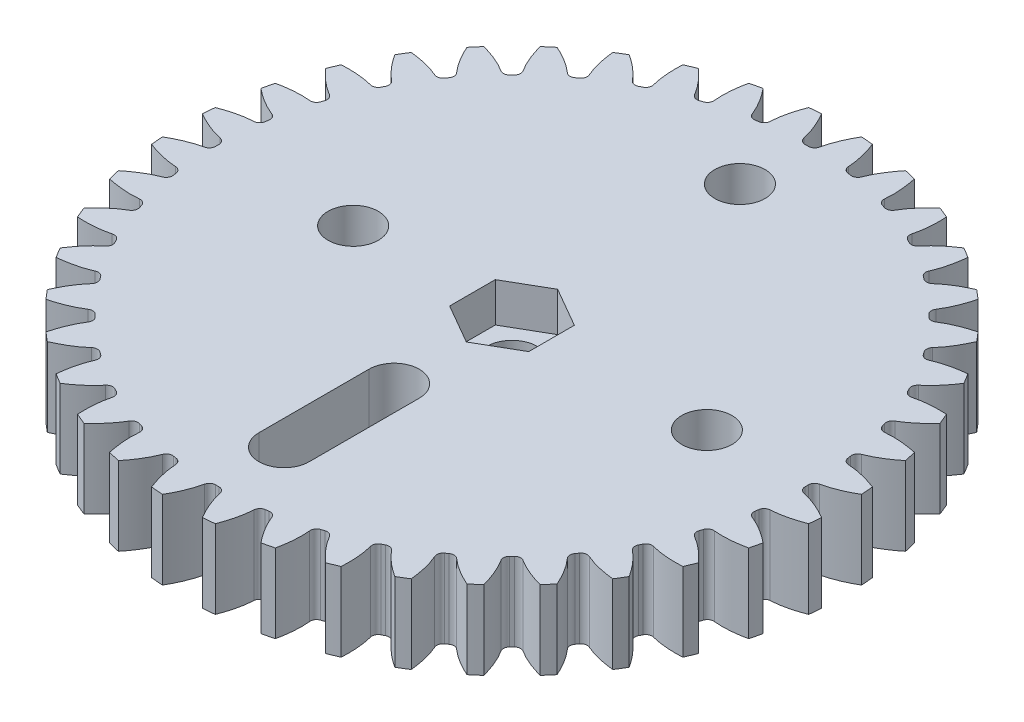
SolidWorks part; units mm, degrees
ref_plane "Front Plane" through (0, 0, 0) normal (0, 0, 1) x (1, 0, 0)
ref_plane "Top Plane" through (0, 0, 0) normal (0, 1, 0) x (1, 0, 0)
ref_plane "Right Plane" through (0, 0, 0) normal (1, 0, 0) x (0, 0, -1)
sketch "Sketch2" plane through (0, 0, 0) normal (0, 1, 0) x (1, 0, 0)
  circle A0 centre (0, 0) radius 53.34
  dimension "D1" = 106.68
extrude "Boss-Extrude1" add sketch "Sketch2" along normal blind 12.7
sketch "Sketch3" plane through (0, 0, 0) normal (0, -1, 0) x (-1, 0, 0)
  line L0 (0, 0) -> (47.7222, -1.163) construction
  line L1 (0, 0) -> (47.7222, 1.163) construction
  line L2 (47.7222, -1.163) -> (47.6109, -1.1603)
  line L3 (47.7222, 1.163) -> (47.6109, 1.1603)
  circle A0 centre (0, 0) radius 53.34
  circle A1 centre (0, 0) radius 50.8
  circle A2 centre (0, 0) radius 47.752
  circle A3 centre (0, 0) radius 47.625
  spline S0 degree 4 poles (47.7222, 1.163) (47.731, 1.1633) (47.7556, 1.1645) (47.802, 1.1678) (47.8777, 1.1747) (47.9741, 1.186) (48.0986, 1.2033) (48.2451, 1.2271) (48.4058, 1.257) (48.5805, 1.2934) (48.7546, 1.3332) (48.928, 1.3762) (49.1005, 1.4219) (49.3093, 1.4808) (49.5592, 1.5562) (49.8507, 1.6513) (50.1805, 1.7675) (50.5158, 1.8948) (50.845, 2.0273) (51.1768, 2.1695) (51.4972, 2.313) (51.8289, 2.4707) (52.1347, 2.6205) (52.4761, 2.7979) (52.7513, 2.9438) (53.113, 3.1463) (53.3263, 3.2689) (53.5754, 3.4159) (53.6857, 3.483) (53.7537, 3.5243) knots 0 0 0 0 0 0.005377 0.015084 0.028532 0.04661 0.064855 0.092111 0.119476 0.146842 0.174209 0.201575 0.228941 0.256307 0.307035 0.361767 0.4165 0.471232 0.525964 0.580697 0.635429 0.690161 0.744894 0.799626 0.854358 0.909091 0.954545 1 1 1 1 1 construction
  spline S1 degree 4 poles (47.7222, 1.163) (47.731, 1.1633) (47.7556, 1.1645) (47.802, 1.1678) (47.8777, 1.1747) (47.9741, 1.186) (48.0986, 1.2033) (48.2451, 1.2271) (48.4058, 1.257) (48.5805, 1.2934) (48.7546, 1.3332) (48.928, 1.3762) (49.1005, 1.4219) (49.3093, 1.4808) (49.5592, 1.5562) (49.8507, 1.6513) (50.1805, 1.7675) (50.5158, 1.8948) (50.845, 2.0273) (51.1768, 2.1695) (51.4972, 2.313) (51.8289, 2.4707) (52.1347, 2.6205) (52.4761, 2.7979) (52.7513, 2.9438) (53.0346, 3.1024) (53.1723, 3.1808) (53.2426, 3.2213) knots 0 0 0 0 0 0.005377 0.015084 0.028532 0.04661 0.064855 0.092111 0.119476 0.146842 0.174209 0.201575 0.228941 0.256307 0.307035 0.361767 0.4165 0.471232 0.525964 0.580697 0.635429 0.690161 0.744894 0.799626 0.854358 0.909091 0.909091 0.909091 0.909091 0.909091
  spline S2 degree 4 poles (47.7222, -1.163) (47.731, -1.1633) (47.7556, -1.1645) (47.802, -1.1678) (47.8777, -1.1747) (47.9741, -1.186) (48.0986, -1.2033) (48.2451, -1.2271) (48.4058, -1.257) (48.5805, -1.2934) (48.7546, -1.3332) (48.928, -1.3762) (49.1005, -1.4219) (49.3093, -1.4808) (49.5592, -1.5562) (49.8507, -1.6513) (50.1805, -1.7675) (50.5158, -1.8948) (50.845, -2.0273) (51.1768, -2.1695) (51.4972, -2.313) (51.8289, -2.4707) (52.1347, -2.6205) (52.4761, -2.7979) (52.7513, -2.9438) (53.113, -3.1463) (53.3263, -3.2689) (53.5754, -3.4159) (53.6857, -3.483) (53.7537, -3.5243) knots 0 0 0 0 0 0.005377 0.015084 0.028532 0.04661 0.064855 0.092111 0.119476 0.146842 0.174209 0.201575 0.228941 0.256307 0.307035 0.361767 0.4165 0.471232 0.525964 0.580697 0.635429 0.690161 0.744894 0.799626 0.854358 0.909091 0.954545 1 1 1 1 1 construction
  spline S3 degree 4 poles (47.7222, -1.163) (47.731, -1.1633) (47.7556, -1.1645) (47.802, -1.1678) (47.8777, -1.1747) (47.9741, -1.186) (48.0986, -1.2033) (48.2451, -1.2271) (48.4058, -1.257) (48.5805, -1.2934) (48.7546, -1.3332) (48.928, -1.3762) (49.1005, -1.4219) (49.3093, -1.4808) (49.5592, -1.5562) (49.8507, -1.6513) (50.1805, -1.7675) (50.5158, -1.8948) (50.845, -2.0273) (51.1768, -2.1695) (51.4972, -2.313) (51.8289, -2.4707) (52.1347, -2.6205) (52.4761, -2.7979) (52.7513, -2.9438) (53.0346, -3.1024) (53.1723, -3.1808) (53.2426, -3.2213) knots 0 0 0 0 0 0.005377 0.015084 0.028532 0.04661 0.064855 0.092111 0.119476 0.146842 0.174209 0.201575 0.228941 0.256307 0.307035 0.361767 0.4165 0.471232 0.525964 0.580697 0.635429 0.690161 0.744894 0.799626 0.854358 0.909091 0.909091 0.909091 0.909091 0.909091
  dimension "D1" = 106.68
  dimension "D2" = 101.6
  dimension "D3" = 95.504
  dimension "D4" = 95.25
extrude "Cut-Extrude1" cut sketch "Sketch3" against normal blind 12.7 contours A1 S3 A0 S1 | A2 S3 A1 S1 | L2 S3 A2 S1 L3 A3 region at (-47.6838, 0, 0) region at (-49.4115, 0, 0) region at (-52.1487, 0, 0)
fillet "Fillet2" radius 1.016 2 edges at (-47.6109, 6.35, -1.1603) (-47.6109, 6.35, 1.1603)
pattern_circular "CirPattern1" count 40 over 360 about axis through (0, 12.7, 0) along (0, 1, 0) of "Fillet2", "Cut-Extrude1"
sketch "Sketch4" plane through (0, 12.7, 0) normal (0, 1, 0) x (1, 0, 0)
  circle A0 centre (0, 0) radius 4.0957
  dimension "D1" = 8.1915
extrude "Cut-Extrude2" cut sketch "Sketch4" against normal through all
sketch "Sketch5" plane through (0, 12.7, 0) normal (0, 1, 0) x (1, 0, 0)
  line L1 (0, 7.3763) -> (-6.3881, 3.6882)
  line L2 (-6.3881, 3.6882) -> (-6.3881, -3.6882)
  line L3 (-6.3881, -3.6882) -> (0, -7.3763)
  line L4 (0, -7.3763) -> (6.3881, -3.6882)
  line L5 (6.3881, -3.6882) -> (6.3881, 3.6882)
  line L6 (6.3881, 3.6882) -> (0, 7.3763)
  circle A0 centre (0, 0) radius 6.3881 construction
  dimension "D1" = 12.7762
extrude "Cut-Extrude3" cut sketch "Sketch5" against normal blind 6.35
sketch "Sketch6" plane through (0, 12.7, 0) normal (0, 1, 0) x (1, 0, 0)
  line L0 (0, 0) -> (0, 36.83) construction
  line L1 (47.6243, -0.2629) -> (-47.6243, -0.2629) construction
  line L2 (0, 0) -> (0, -47.625) construction
  line L3 (0, -19.05) -> (0, -36.83) construction
  line L4 (4.064, -19.05) -> (4.064, -36.83)
  line L5 (-4.064, -19.05) -> (-4.064, -36.83)
  circle A0 centre (0, 36.83) radius 4.064
  arc A1 (-0.2629, -47.6243) -> (0.2629, -47.6243) centre (0, 0) ccw construction
  circle A2 centre (31.75, -0.2629) radius 4.064
  circle A3 centre (-25.4, -0.2629) radius 4.064
  arc A4 (4.064, -19.05) -> (-4.064, -19.05) centre (0, -19.05) ccw
  arc A5 (-4.064, -36.83) -> (4.064, -36.83) centre (0, -36.83) ccw
  point P18 (0, -27.94)
  dimension "D2" = 8.128
  dimension "D3" = 8.128
  dimension "D4" = 8.128
  dimension "D7" = 4.064
  dimension "D1" = 36.83
  dimension "D5" = 31.75
  dimension "D6" = 25.4
  dimension "D8" = 36.83
  dimension "D9" = 19.05
extrude "Cut-Extrude4" cut sketch "Sketch6" against normal through all both and the other way through all
equation "\"DiametralPitch\"= 10"
equation "\"NumTeeth\"= 40"
equation "\"PressureAngle\"= 20deg"
equation "\"Addendum\"= 1 / \"DiametralPitch\""
equation "\"Dedendum\"= 1.25 / \"DiametralPitch\""
equation "\"WorkingDepth\"= 2 / \"DiametralPitch\""
equation "\"WholeDepth\"= 2.25 / \"DiametralPitch\""
equation "\"Clearance\"= 0.3 / \"DiametralPitch\""
equation "\"ToothThickness\"= 1.5708 / \"DiametralPitch\""
equation "\"CircularPitch\"= pi / \"DiametralPitch\""
equation "\"PitchCircle\"= \"NumTeeth\" / \"DiametralPitch\""
equation "\"OutsideDiameter\"= ( \"NumTeeth\" + 2 ) / \"DiametralPitch\""
equation "\"Fillet\"= \"Clearance\" * cos ( \"PressureAngle\" ) * tan ( ( 90 + \"PressureAngle\" ) / 2 )"
equation "\"AddendumCircle\"= \"PitchCircle\" + ( 2 * \"Addendum\" )"
equation "\"DedendumCircle\"= \"PitchCircle\" - ( 2 * \"Dedendum\" )"
equation "\"BaseCircle\"= \"PitchCircle\" * cos ( \"PressureAngle\" )"
equation "\"PitchAngle\"= 360deg / \"NumTeeth\""
equation "\"Alpha\"= sqr ( \"PitchCircle\" ^ 2 - \"BaseCircle\" ^ 2 ) / \"BaseCircle\" * 180 / PI - \"PressureAngle\""
equation "\"Beta\"= ( \"PitchAngle\" / 4 - \"Alpha\" )"
equation "\"Phi\"= sqr ( ( \"AddendumCircle\" / 2 ) ^ 2 - ( \"BaseCircle\" / 2 ) ^ 2 ) / ( \"BaseCircle\" / 2 )"
